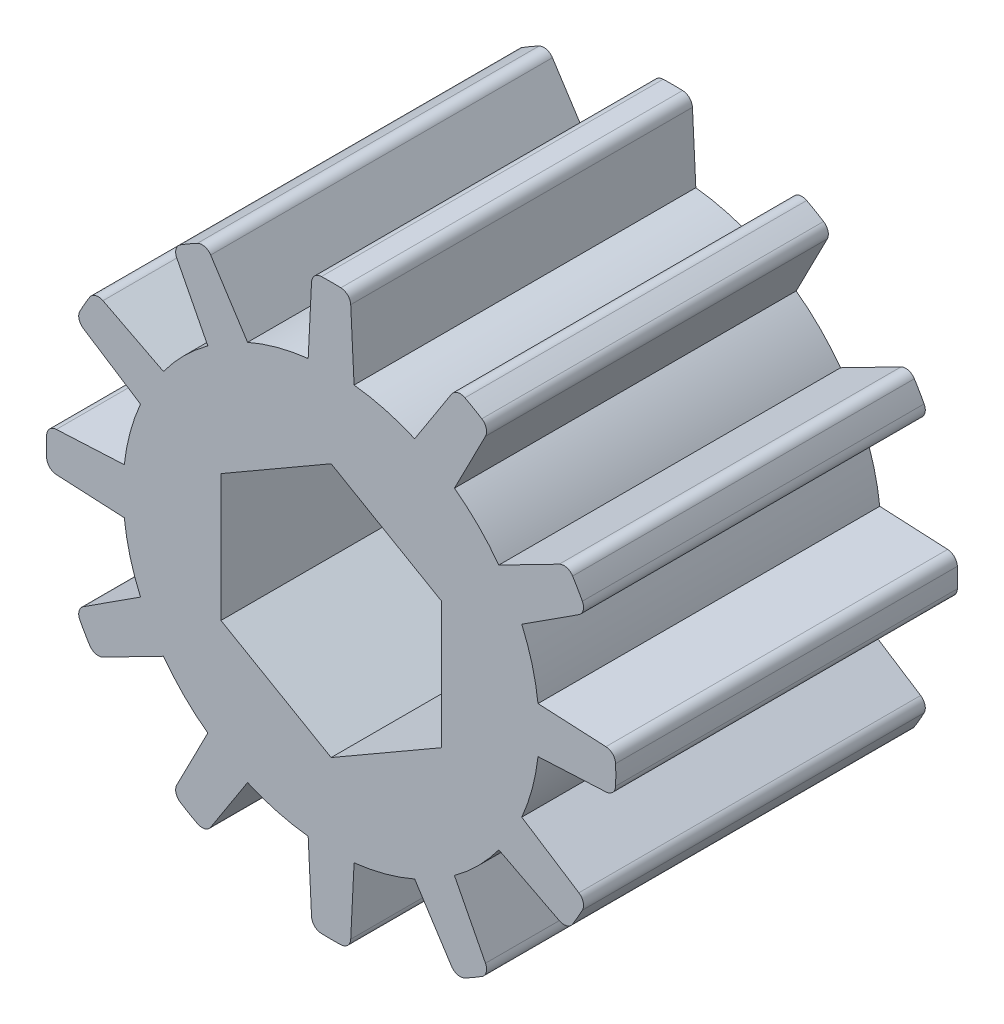
SolidWorks part; units mm, degrees
material "ABS"
ref_plane "Alzado" through (0, 0, 0) normal (0, 0, 1) x (1, 0, 0)
ref_plane "Planta" through (0, 0, 0) normal (0, 1, 0) x (1, 0, 0)
ref_plane "Vista lateral" through (0, 0, 0) normal (1, 0, 0) x (0, 0, -1)
sketch "Croquis1" plane through (0, 0, 0) normal (0, 0, 1) x (1, 0, 0)
  line L0 (0, 0) -> (0, 4.6049) construction
  line L1 (0.375, 5.5679) -> (0.45, 4.0556)
  line L2 (-0.375, 5.5679) -> (-0.45, 4.0556)
  line L3 (2.4592, 5.0094) -> (1.6381, 3.7373)
  line L4 (3.1087, 4.6344) -> (2.4175, 3.2873)
  line L5 (4.6344, 3.1087) -> (3.2873, 2.4175)
  line L6 (5.0094, 2.4592) -> (3.7373, 1.6381)
  line L7 (5.5679, 0.375) -> (4.0556, 0.45)
  line L8 (5.5679, -0.375) -> (4.0556, -0.45)
  line L9 (5.0094, -2.4592) -> (3.7373, -1.6381)
  line L10 (4.6344, -3.1087) -> (3.2873, -2.4175)
  line L11 (3.1087, -4.6344) -> (2.4175, -3.2873)
  line L12 (2.4592, -5.0094) -> (1.6381, -3.7373)
  line L13 (0.375, -5.5679) -> (0.45, -4.0556)
  line L14 (-0.375, -5.5679) -> (-0.45, -4.0556)
  line L15 (-2.4592, -5.0094) -> (-1.6381, -3.7373)
  line L16 (-3.1087, -4.6344) -> (-2.4175, -3.2873)
  line L17 (-4.6344, -3.1087) -> (-3.2873, -2.4175)
  line L18 (-5.0094, -2.4592) -> (-3.7373, -1.6381)
  line L19 (-5.5679, -0.375) -> (-4.0556, -0.45)
  line L20 (-5.5679, 0.375) -> (-4.0556, 0.45)
  line L21 (-5.0094, 2.4592) -> (-3.7373, 1.6381)
  line L22 (-4.6344, 3.1087) -> (-3.2873, 2.4175)
  line L23 (-3.1087, 4.6344) -> (-2.4175, 3.2873)
  line L24 (-2.4592, 5.0094) -> (-1.6381, 3.7373)
  circle A0 centre (0, 0) radius 1.85
  arc A1 (1.6381, 3.7373) -> (0.45, 4.0556) centre (0, 0) ccw
  arc A2 (3.1087, 4.6344) -> (2.4592, 5.0094) centre (0, 0) ccw
  arc A3 (5.0094, 2.4592) -> (4.6344, 3.1087) centre (0, 0) ccw
  arc A4 (5.5679, -0.375) -> (5.5679, 0.375) centre (0, 0) ccw
  arc A5 (4.6344, -3.1087) -> (5.0094, -2.4592) centre (0, 0) ccw
  arc A6 (2.4592, -5.0094) -> (3.1087, -4.6344) centre (0, 0) ccw
  arc A7 (-0.375, -5.5679) -> (0.375, -5.5679) centre (0, 0) ccw
  arc A8 (-3.1087, -4.6344) -> (-2.4592, -5.0094) centre (0, 0) ccw
  arc A9 (-5.0094, -2.4592) -> (-4.6344, -3.1087) centre (0, 0) ccw
  arc A10 (-5.5679, 0.375) -> (-5.5679, -0.375) centre (0, 0) ccw
  arc A11 (-4.6344, 3.1087) -> (-5.0094, 2.4592) centre (0, 0) ccw
  arc A12 (-2.4592, 5.0094) -> (-3.1087, 4.6344) centre (0, 0) ccw
  arc A13 (0.375, 5.5679) -> (-0.375, 5.5679) centre (0, 0) ccw
  arc A14 (3.2873, 2.4175) -> (2.4175, 3.2873) centre (0, 0) ccw
  arc A15 (4.0556, 0.45) -> (3.7373, 1.6381) centre (0, 0) ccw
  arc A16 (3.7373, -1.6381) -> (4.0556, -0.45) centre (0, 0) ccw
  arc A17 (2.4175, -3.2873) -> (3.2873, -2.4175) centre (0, 0) ccw
  arc A18 (0.45, -4.0556) -> (1.6381, -3.7373) centre (0, 0) ccw
  arc A19 (-1.6381, -3.7373) -> (-0.45, -4.0556) centre (0, 0) ccw
  arc A20 (-3.2873, -2.4175) -> (-2.4175, -3.2873) centre (0, 0) ccw
  arc A21 (-4.0556, -0.45) -> (-3.7373, -1.6381) centre (0, 0) ccw
  arc A22 (-3.7373, 1.6381) -> (-4.0556, 0.45) centre (0, 0) ccw
  arc A23 (-2.4175, 3.2873) -> (-3.2873, 2.4175) centre (0, 0) ccw
  arc A24 (-0.45, 4.0556) -> (-1.6381, 3.7373) centre (0, 0) ccw
  dimension "D1" = 0.9
  dimension "D2" = 3.7
  dimension "D4" = 1.5
  dimension "D3" = 0.75
  dimension "D6" = 1.23
  dimension "D5" = 12
extrude "Saliente-Extruir1" add sketch "Croquis1" along normal blind 6.7
sketch "Croquis10" plane through (0, 0, 0) normal (0, 0, -1) x (-1, 0, 0)
  line L1 (0, -2.4942) -> (2.16, -1.2471)
  line L2 (2.16, -1.2471) -> (2.16, 1.2471)
  line L3 (2.16, 1.2471) -> (0, 2.4942)
  line L4 (0, 2.4942) -> (-2.16, 1.2471)
  line L5 (-2.16, 1.2471) -> (-2.16, -1.2471)
  line L6 (-2.16, -1.2471) -> (0, -2.4942)
  circle A0 centre (0, 0) radius 2.16 construction
  dimension "D1" = 4.32
extrude "Cortar-Extruir3" cut sketch "Croquis10" against normal through all
fillet "Redondeo1" radius 0.2 24 edges at (5.5679, -0.375, 3.35) (-2.4592, -5.0094, 3.35) (-3.1087, -4.6344, 3.35) (0.375, -5.5679, 3.35) (-0.375, -5.5679, 3.35) (3.1087, -4.6344, 3.35) (2.4592, -5.0094, 3.35) (5.0094, -2.4592, 3.35) (4.6344, -3.1087, 3.35) (-4.6344, -3.1087, 3.35) (-5.0094, -2.4592, 3.35) (-5.5679, -0.375, 3.35) (-5.5679, 0.375, 3.35) (-5.0094, 2.4592, 3.35) (-4.6344, 3.1087, 3.35) (-3.1087, 4.6344, 3.35) (-2.4592, 5.0094, 3.35) (5.5679, 0.375, 3.35) (5.0094, 2.4592, 3.35) (4.6344, 3.1087, 3.35) (3.1087, 4.6344, 3.35) (2.4592, 5.0094, 3.35) (0.375, 5.5679, 3.35) (-0.375, 5.5679, 3.35)
